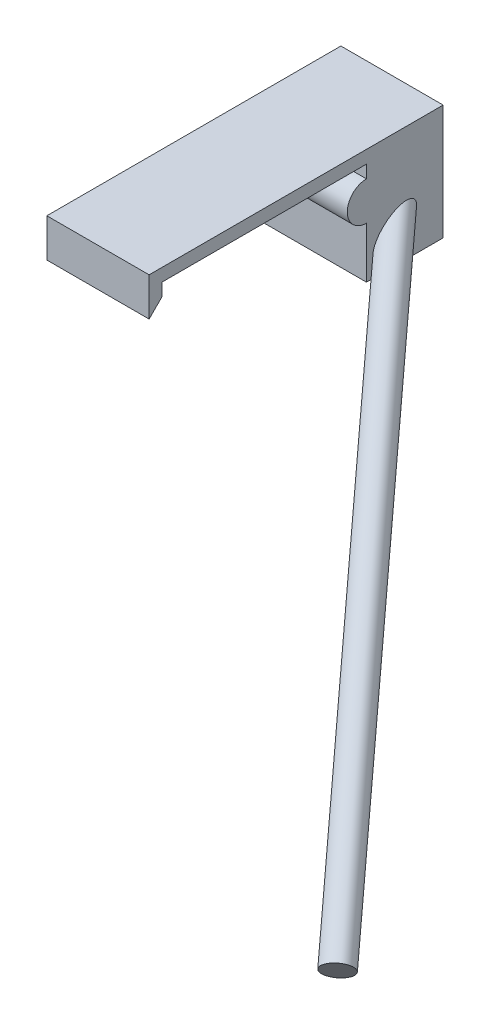
SolidWorks part; units mm, degrees
ref_plane "Front Plane" through (0, 0, 0) normal (0, 0, 1) x (1, 0, 0)
ref_plane "Top Plane" through (0, 0, 0) normal (0, 1, 0) x (1, 0, 0)
ref_plane "Right Plane" through (0, 0, 0) normal (1, 0, 0) x (0, 0, -1)
sketch "Sketch1" plane through (0, 0, 0) normal (0, 1, 0) x (1, 0, 0)
  line L1 (-19.05, -25.4) -> (19.05, -25.4)
  line L2 (-19.05, -25.4) -> (-19.05, 25.4)
  line L3 (-19.05, 25.4) -> (19.05, 25.4)
  line L4 (19.05, -25.4) -> (19.05, 25.4)
  line L5 (-19.05, -25.4) -> (19.05, 25.4) construction
  line L6 (-19.05, 25.4) -> (19.05, -25.4) construction
  point P0 (0, 0)
  dimension "D1" = 50.8
  dimension "D2" = 38.1
extrude "Boss-Extrude1" add sketch "Sketch1" along normal blind 3.175
sketch "Sketch2" plane through (0, 3.175, 0) normal (0, 1, 0) x (1, 0, 0)
  line L0 (-19.05, 25.4) -> (19.05, 25.4)
  line L1 (-19.05, 25.4) -> (-19.05, 44.45)
  line L2 (-19.05, 44.45) -> (19.05, 44.45)
  line L3 (19.05, 44.45) -> (19.05, 25.4)
  dimension "D1" = 19.05
extrude "Boss-Extrude2" add sketch "Sketch2" against normal blind 28.575
ref_plane "LeftRotationPlane" through (3.175, -3.175, 0) normal (-0.7071, 0.7071, 0) x (0, 0, 1)
sketch "Sketch5" plane through (3.175, -3.175, 0) normal (-0.7071, 0.7071, 0) x (0, 0, 1)
  line L0 (-25.4, -31.4309) -> (-25.4, 4.4901)
  line L1 (-25.4, -31.4309) -> (-25.4, 4.4901)
ref_plane "DownRotationPlane" through (-6.9807, 6.9807, -8.2837) normal (-0.5417, 0.5417, -0.6428) x (0.7071, 0.7071, 0)
sketch "Sketch3" plane through (-6.9807, 6.9807, -8.2837) normal (-0.5417, 0.5417, -0.6428) x (0.7071, 0.7071, 0)
  circle A0 centre (0, -23.4078) radius 3.4925
  dimension "D1" = 6.985
sketch "Sketch4" plane through (-6.9807, 6.9807, -8.2837) normal (-0.5417, 0.5417, -0.6428) x (0.7071, 0.7071, 0)
  line L1 (-31.4309, 36.9369) -> (-11.2253, 23.949) construction
  line L2 (-31.4309, 36.9369) -> (-11.2253, 23.949) construction
  circle A0 centre (0.9676, 41.5415) radius 3.4925
  point P4 (-5.1222, 40.2279)
  point P5 (-6.5876, 39.1623)
  point P6 (0, 0)
  point P7 (-5.0946, 30.7723)
  point P8 (-2.4157, 37.2077)
  point P9 (0, 37.1381)
  point P10 (0.9676, 41.5415)
  dimension "D1" = 6.985
extrude "ActualHoleForTubing" [suppressed] cut sketch "Sketch4" along normal through all and the other way through all
extrude "ImaginaryTubing" add sketch "Sketch4<2>" against normal blind 152.4 and the other way blind 12.7
sketch "Sketch4<2>" plane through (-6.9807, 6.9807, -8.2837) normal (-0.5417, 0.5417, -0.6428) x (0.7071, 0.7071, 0) same geometry as "Sketch4"
sketch "Sketch6" plane through (-19.05, 0, 0) normal (-1, 0, 0) x (0, 0, 1)
  line L6 (-25.4, 0) -> (25.4, 0)
  line L7 (25.4, 0) -> (25.4, 3.175)
  line L8 (25.4, 3.175) -> (-44.45, 3.175)
  line L9 (-44.45, 3.175) -> (-44.45, -25.4)
  line L10 (-44.45, -25.4) -> (-25.4, -25.4)
  line L11 (-25.4, -25.4) -> (-25.4, 0)
  line L12 (-25.4, 0) -> (25.4, 0)
  line L13 (25.4, 0) -> (25.4, 3.175)
  line L14 (25.4, 3.175) -> (-44.45, 3.175)
  line L15 (-44.45, 3.175) -> (-44.45, -25.4)
  line L16 (-44.45, -25.4) -> (-25.4, -25.4)
  line L17 (-25.4, -25.4) -> (-25.4, 0)
  dimension "D1" = 0
extrude "Cut-Extrude1" cut sketch "Sketch6" against normal blind 12.7
sketch "Sketch7" plane through (0, 0, 25.4) normal (0, 0, 1) x (1, 0, 0)
  line L0 (-6.35, 0) -> (19.05, 0) construction
  line L1 (19.05, 3.175) -> (-6.35, 3.175)
  line L2 (19.05, 3.175) -> (19.05, -6.35)
  line L3 (19.05, -6.35) -> (-6.35, -6.35)
  line L4 (-6.35, 3.175) -> (-6.35, -6.35)
  dimension "D1" = 9.525
extrude "Boss-Extrude4" add sketch "Sketch7" along normal blind 3.175
sketch "Sketch8" plane through (19.05, 0, 0) normal (1, 0, 0) x (0, 0, -1)
  line L0 (25.4, -25.4) -> (25.4, 0) construction
  line L1 (-25.4, 0) -> (25.4, 0) construction
  line L4 (25.4, -12.7) -> (25.4, -3.175)
  arc A0 (25.4, -3.175) -> (25.4, -12.7) centre (25.4, -7.9375) ccw
  point P0 (25.4, -3.175)
  dimension "D1" = 3.175
extrude "Boss-Extrude5" add sketch "Sketch8" against normal up to surface (25.4 mm away) up to face at (-6.35, -7.1438, -3.9688)
sketch "Sketch11" plane through (19.05, 0, 0) normal (1, 0, 0) x (0, 0, -1)
  line L1 (-25.4, -6.35) -> (-25.4, 0) construction
  line L4 (-25.4, -3.175) -> (-28.575, -6.35)
  line L7 (-28.575, -6.35) -> (-25.4, -6.35)
  line L8 (-25.4, -6.35) -> (-25.4, -3.175)
extrude "Cut-Extrude2" cut sketch "Sketch11" against normal up to surface (25.4 mm away) up to face at (-6.35, -7.3025, -7.7788)
